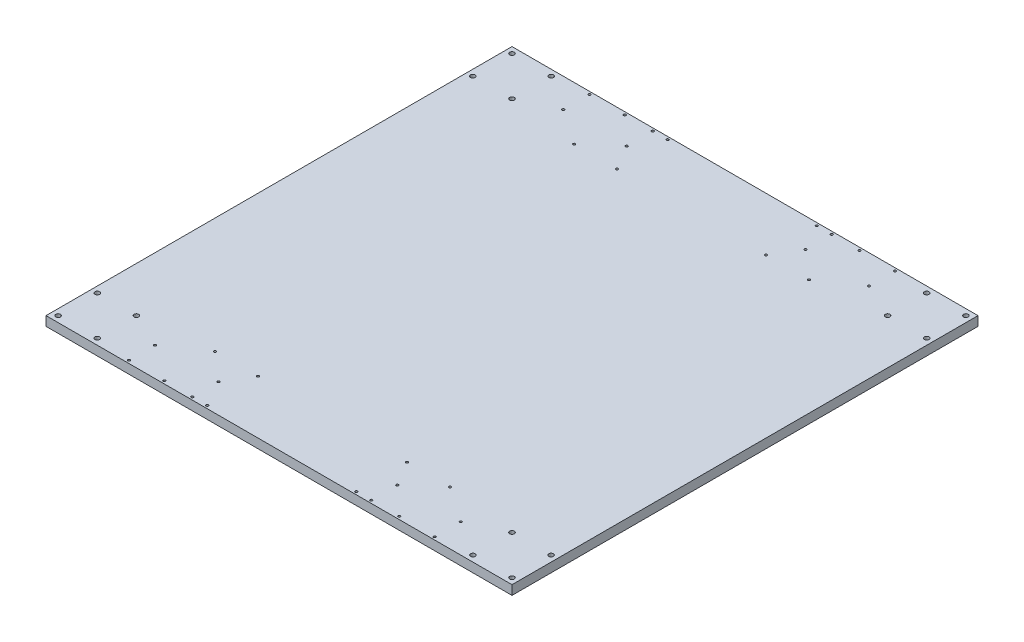
SolidWorks part; units mm, degrees
material "AISI 1045 Steel, cold drawn"
ref_plane "Front Plane" through (0, 0, 0) normal (0, 0, 1) x (1, 0, 0)
ref_plane "Top Plane" through (0, 0, 0) normal (0, 1, 0) x (1, 0, 0)
ref_plane "Right Plane" through (0, 0, 0) normal (1, 0, 0) x (0, 0, -1)
sketch "Sketch1" plane through (0, 0, 0) normal (0, 1, 0) x (1, 0, 0)
  line L1 (250, -250) -> (-250, -250)
  line L2 (250, -250) -> (250, 250)
  line L3 (250, 250) -> (-250, 250)
  line L4 (-250, -250) -> (-250, 250)
  line L5 (250, -250) -> (-250, 250) construction
  line L6 (250, 250) -> (-250, -250) construction
  point P0 (0, 0)
  dimension "D1" = 500
extrude "Boss-Extrude1" add sketch "Sketch1" along normal blind 10
sketch "Sketch2" plane through (0, 10, 0) normal (0, 1, 0) x (1, 0, 0)
  line L0 (250, -250) -> (250, 250) construction
  line L1 (164, -247) -> (96, -247)
  line L2 (164, -247) -> (164, -219)
  line L3 (164, -219) -> (96, -219)
  line L4 (96, -247) -> (96, -219)
  line L5 (-250, -250) -> (250, -250) construction
  line L6 (0, -1000) -> (0, 49000) construction
  line L7 (-96, -247) -> (-96, -219)
  line L8 (-164, -219) -> (-96, -219)
  line L9 (-164, -247) -> (-164, -219)
  line L10 (-164, -247) -> (-96, -247)
  line L11 (-1000, 0) -> (49000, 0) construction
  line L12 (-164, 247) -> (-96, 247)
  line L13 (-164, 247) -> (-164, 219)
  line L14 (-164, 219) -> (-96, 219)
  line L15 (-96, 247) -> (-96, 219)
  line L16 (96, 247) -> (96, 219)
  line L17 (164, 219) -> (96, 219)
  line L18 (164, 247) -> (164, 219)
  line L19 (164, 247) -> (96, 247)
  line L20 (-126, -192.6) -> (-80, -192.6)
  line L21 (126, -247) -> (80, -247)
  line L22 (126, -247) -> (126, -192.6)
  line L23 (126, -192.6) -> (80, -192.6)
  line L24 (80, -247) -> (80, -192.6)
  line L25 (-80, -247) -> (-80, -192.6)
  line L26 (-126, -247) -> (-80, -247)
  line L27 (-126, -247) -> (-126, -192.6)
  line L28 (126, 192.6) -> (80, 192.6)
  line L29 (80, 247) -> (80, 192.6)
  line L30 (126, 247) -> (80, 247)
  line L31 (126, 247) -> (126, 192.6)
  line L32 (-126, 247) -> (-126, 192.6)
  line L33 (-126, 247) -> (-80, 247)
  line L34 (-80, 247) -> (-80, 192.6)
  line L35 (-126, 192.6) -> (-80, 192.6)
  dimension "D1" = 86
  dimension "D2" = 68
  dimension "D3" = 28
  dimension "D4" = 3
  dimension "D5" = 30
  dimension "D6" = 46
  dimension "D7" = 54.4
hole_wizard "Tap Drill for M3x0.5 Tap1" positions "Sketch3" profile "Sketch4" hole size "M3x0.5" standard "ANSI Metric" end condition through all
sketch "Sketch3" plane through (0, 10, 0) normal (0, 1, 0) x (1, 0, 0)
  point P0 (164, -219)
  point P3 (164, -247)
  point P6 (96, -247)
  point P9 (96, -219)
  point P12 (-96, -219)
  point P15 (-164, -219)
  point P18 (-164, -247)
  point P21 (-96, -247)
  point P24 (-96, 219)
  point P27 (-96, 247)
  point P30 (-164, 247)
  point P33 (-164, 219)
  point P36 (96, 247)
  point P39 (164, 247)
  point P42 (164, 219)
  point P45 (96, 219)
  point P48 (-126, 247)
  point P51 (-80, 247)
  point P54 (-80, 192.6)
  point P56 (-126, 192.6)
  point P62 (80, 247)
  point P65 (126, 247)
  point P68 (126, 192.6)
  point P71 (80, 192.6)
  point P74 (80, -192.6)
  point P77 (126, -192.6)
  point P80 (126, -247)
  point P83 (80, -247)
  point P86 (-126, -192.6)
  point P89 (-80, -192.6)
  point P92 (-80, -247)
  point P95 (-126, -247)
sketch "Sketch4" plane through (164, 10, 219) normal (1, 0, 0) x (0, 0, 1)
  line L0 (0, 0) -> (0, 10)
  line L1 (0, 10) -> (1.25, 10)
  line L2 (1.25, 10) -> (1.25, 0)
  line L5 (1.25, 0) -> (0, 0)
  line L11 (0, -6.35) -> (0, 107.95) construction
  dimension "Thru Hole Dia." = 2.5
  dimension "Thru Hole Depth" = 10
hole_wizard "Tap Drill for M6x1.0 Tap1" positions "Sketch5" profile "Sketch6" hole size "M6x1.0" standard "ANSI Metric" end condition through all
sketch "Sketch5" plane through (0, 10, 0) normal (0, 1, 0) x (1, 0, 0)
  line L1 (243.5, -243.5) -> (201.5, -243.5)
  line L2 (243.5, -243.5) -> (243.5, -201.5)
  line L3 (243.5, -201.5) -> (201.5, -201.5)
  line L4 (201.5, -243.5) -> (201.5, -201.5)
  line L5 (201.5, -243.5) -> (243.5, -201.5) construction
  line L7 (250, -250) -> (250, 250) construction
  line L8 (-250, -250) -> (250, -250) construction
  circle A0 centre (222.5, -222.5) radius 27.5
  point P1 (243.5, -243.5)
  point P2 (201.5, -201.5)
  point P39 (243.5, -201.5)
  point P40 (201.5, -243.5)
  dimension "D3" = 55
  dimension "D1" = 42
  dimension "D2" = 42
sketch "Sketch6" plane through (243.5, 10, 243.5) normal (1, 0, 0) x (0, 0, 1)
  line L0 (0, 0) -> (0, 10)
  line L1 (0, 10) -> (2.5, 10)
  line L2 (2.5, 10) -> (2.5, 0)
  line L5 (2.5, 0) -> (0, 0)
  line L11 (0, -6.35) -> (0, 107.95) construction
  dimension "Thru Hole Dia." = 5
  dimension "Thru Hole Depth" = 10
ref_axis "Axis1" through (0, 10.5, 0) along (0, -1, 0)
pattern_circular "CirPattern1" count 4 over 360 about axis through (0, 10.5, 0) along (0, -1, 0) of "Tap Drill for M6x1.0 Tap1"
